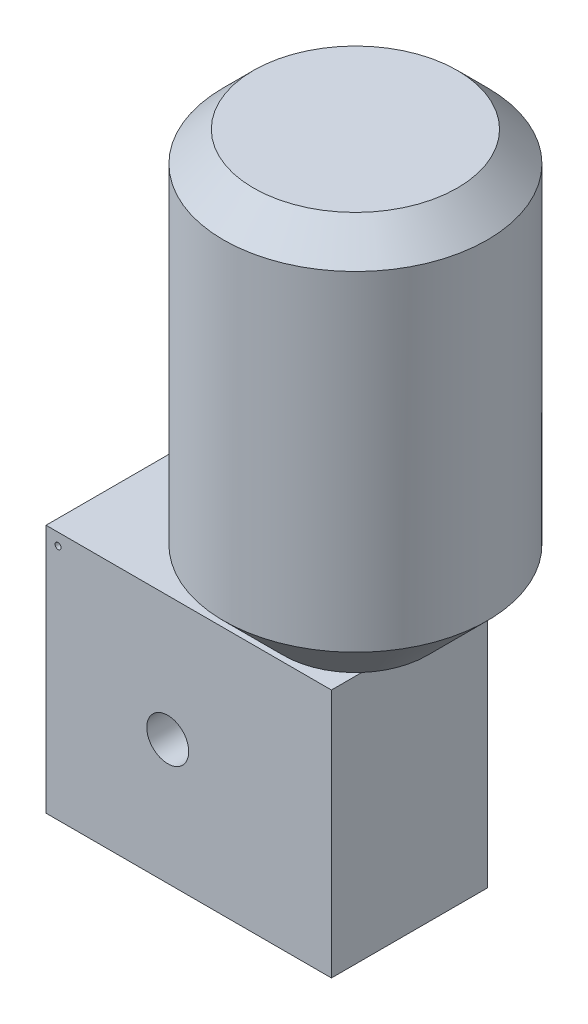
SolidWorks part; units mm, degrees
material "201 Annealed Stainless Steel (SS)"
ref_plane "Front Plane" through (0, 0, 0) normal (0, 0, 1) x (1, 0, 0)
ref_plane "Top Plane" through (0, 0, 0) normal (0, 1, 0) x (1, 0, 0)
ref_plane "Right Plane" through (0, 0, 0) normal (1, 0, 0) x (0, 0, -1)
sketch "Sketch1" plane through (0, 0, 0) normal (0, 0, 1) x (1, 0, 0)
  line L8 (35, 0) -> (273, 0)
  line L9 (273, 0) -> (273, 208)
  line L10 (273, 208) -> (35, 208)
  line L11 (35, 208) -> (35, 0)
  circle A1 centre (136.5, 104) radius 17.5
  circle A3 centre (45, 198) radius 2.5
extrude "Boss-Extrude1" add sketch "Sketch1" against normal blind 130
ref_plane "Plane1" through (0, 0, -65) normal (0, 0, 1) x (1, 0, 0)
sketch "Sketch3" plane through (0, 208, 0) normal (0, 1, 0) x (1, 0, 0)
  circle A1 centre (228, 65) radius 110
  point P3 (0, 0)
sketch "Sketch2" plane through (0, 0, -65) normal (0, 0, 1) x (1, 0, 0)
  line L0 (228, 157.8312) -> (228, 597.096) construction
  line L1 (288, 208) -> (338, 258)
  line L2 (338, 258) -> (338, 533)
  line L3 (338, 533) -> (313, 558)
  line L4 (313, 558) -> (228, 558)
  line L8 (228, 208) -> (288, 208)
  line L9 (228, 558) -> (228, 208)
  point P16 (228, 597.096)
  point P17 (289.1128, 209.1128)
  point P18 (228, 558)
revolve "Revolve1" add sketch "Sketch2" angle 360 about L0
